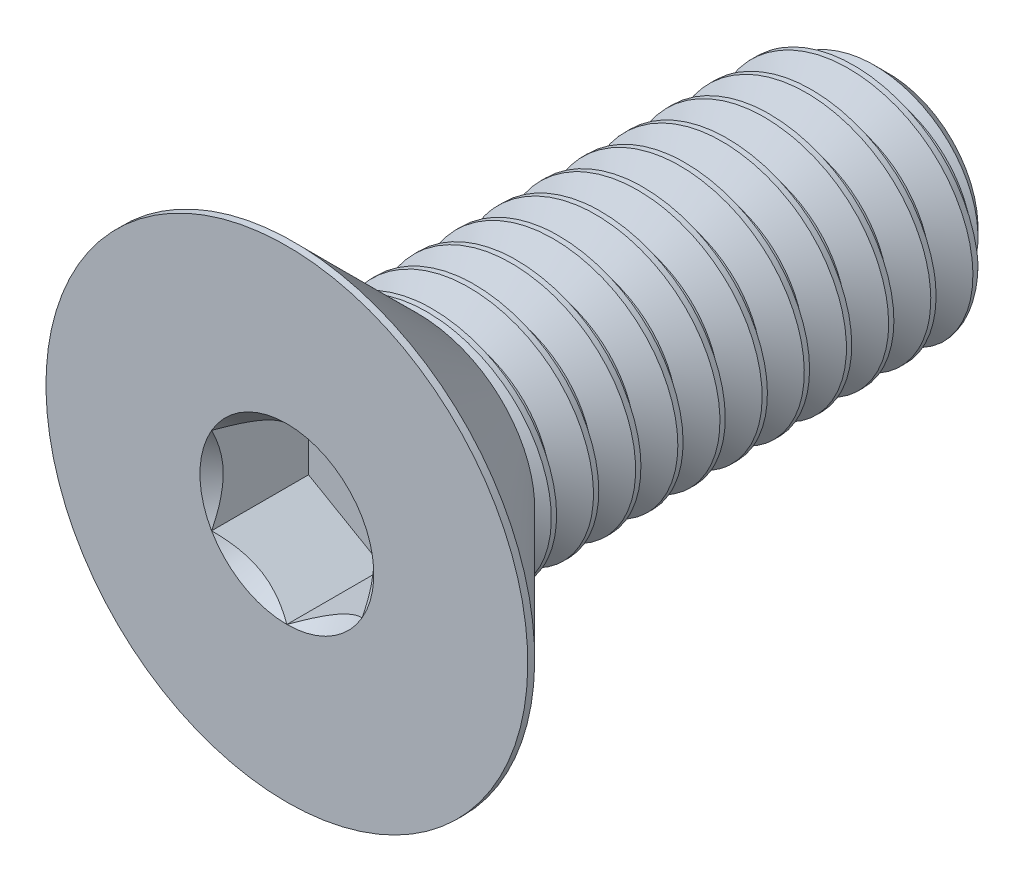
SolidWorks part; units mm, degrees
material "AISI 304"
ref_plane "Front" through (0, 0, 0) normal (0, 0, 1) x (1, 0, 0)
ref_plane "Top" through (0, 0, 0) normal (0, 1, 0) x (1, 0, 0)
ref_plane "Right" through (0, 0, 0) normal (1, 0, 0) x (0, 0, -1)
sketch "Sketch11" plane through (0, 0, 0) normal (1, 0, 0) x (0, 0, -1)
  line L0 (-5, 4) -> (5, 4) construction
  line L5 (-5, 4) -> (-5, -4) construction
  line L6 (5, 2) -> (5, -2) construction
  line L7 (-4.99, 1.25) -> (-4.99, -1.25) construction
  line L8 (4.9562, 2.0758) -> (5.6563, 2.0758) construction
  line L9 (5.6563, 2.0758) -> (5.3062, 1.4696) construction
  line L10 (5.3062, 1.4696) -> (4.9562, 2.0758) construction
  line L11 (5.2625, 1.5453) -> (5.35, 1.5453) construction
  line L12 (5.3062, 1.5453) -> (5.3062, 1.4696) construction
  line L13 (4.9781, 2.0379) -> (5.6344, 2.0379) construction
  line L14 (5.3062, 2.0758) -> (5.3062, 2) construction
  line L15 (5, 2) -> (5.6125, 2) construction
  line L17 (-4.885, 4) -> (-0.885, 0) construction
  line L18 (-0.885, 0) -> (-4.885, -4) construction
  point P3 (-2.7, 4)
  point P8 (0, 4)
  point P21 (5.3062, 2.0379)
  point P26 (-5, 0)
  point P28 (-4.99, 0)
  point P29 (5, 0)
  dimension "Length" = 10
  dimension "Head Diameter" = 8
  dimension "Thread Major Diameter" = 4
  dimension "Head Height" = 2.3
  dimension "Drive Size" = 2.5
  dimension "Thread Pitch" = 0.7
  dimension "D1" = 0.0875
  dimension "D2" = 0.01
  dimension "D3" = 0.115
  dimension "Countersink Angle" = 90
sketch "Sketch1" plane through (0, 0, 0) normal (1, 0, 0) x (0, 0, -1)
  line L2 (-2.7, 2) -> (5, 2)
  line L3 (5, 2) -> (5, 0)
  line L4 (-3.39, 2) -> (-3.39, 0)
  line L5 (-2.7, 2) -> (-3.39, 2)
  line L6 (-5, 4) -> (-5, -4) construction
  line L7 (5, 2) -> (5, -2) construction
  line L8 (-3.39, 0) -> (5, 0)
  dimension "D1" = 1.61
revolve "Revolve1" add sketch "Sketch1" angle 360 mid plane about L8
chamfer "Chamfer1" distance 0.525 angle 45 1 edges at (0, -2, -5)
sketch "Sketch7" plane through (0, 0, 0) normal (1, 0, 0) x (0, 0, -1)
  line L2 (-5, 4) -> (-4.885, 4)
  line L5 (-2.7, 1.815) -> (-2.7, 0)
  line L6 (-5, 4) -> (-5, 0)
  line L8 (-5, 4) -> (-5, -4) construction
  line L9 (-5, 0) -> (-2.7, 0)
  line L12 (-4.885, 4) -> (-2.7, 1.815)
  line L13 (-4.885, 4) -> (-0.885, 0) construction
revolve "Revolve2" add sketch "Sketch7" angle 360 mid plane about L9 region at (0, 1.5544, 3.9977)
ref_plane "Plane1" through (0, 0, 2.7) normal (0, 0, 1) x (1, 0, 0)
sketch "Sketch5" plane through (0, 0, 5) normal (0, 0, 1) x (1, 0, 0)
  line L1 (1.25, -0.7217) -> (1.25, 0.7217)
  line L2 (1.25, 0.7217) -> (0, 1.4434)
  line L3 (0, 1.4434) -> (-1.25, 0.7217)
  line L4 (-1.25, 0.7217) -> (-1.25, -0.7217)
  line L5 (-1.25, -0.7217) -> (0, -1.4434)
  line L6 (0, -1.4434) -> (1.25, -0.7217)
  circle A0 centre (0, 0) radius 1.25 construction
extrude "Cut-Extrude2" cut sketch "Sketch5" against normal blind 1.61
sketch "Sketch6" plane through (0, 0, 5) normal (0, 0, -1) x (-1, 0, 0)
  circle A0 centre (0, 0) radius 1.4434
extrude "Cut-Extrude3" cut sketch "Sketch6" along normal blind 1.61 draft 45
sketch "Sketch12" plane through (0, 0, -5) normal (0, 0, -1) x (-1, 0, 0)
  circle A0 centre (0, 0) radius 2 construction
  circle A1 centre (0, 0) radius 2
curve "Helix/Spiral1" pitch 0.7 height 10 radius 2 centre (0, 0, -5) axis (0, 0, 1) start towards (0, 1, 0)
sketch "Sketch13" plane through (0, 0, 0) normal (1, 0, 0) x (0, 0, -1)
  line L0 (4.9781, 2.0379) -> (5.6344, 2.0379)
  line L1 (5.6344, 2.0379) -> (5.35, 1.5453)
  line L2 (5.35, 1.5453) -> (5.2625, 1.5453)
  line L3 (5.2625, 1.5453) -> (4.9781, 2.0379)
sweep "Cut-Sweep1" cut profiles "Sketch13" path "Helix/Spiral1" align with end faces yes
combine bodies "Combine1" operation type add bodies to combine 113 127
equation "\"D1@Chamfer1\"=\"Thread Pitch@Sketch11\" * .75"
equation "\"D1@Cut-Extrude2\"= \"Head Height@Sketch11\" * .7"
equation "\"D1@Cut-Extrude3\" = \"D1@Cut-Extrude2\""
equation "\"D1@Sketch11\"=\"Thread Pitch@Sketch11\"/8"
equation "\"D3@Sketch11\"=\"Head Height@Sketch11\"*.05"
equation "\"D4@Helix/Spiral1\"=\"Thread Pitch@Sketch11\""
equation "\"D1@Sketch1\"=\"Head Height@Sketch11\"*.7"
equation "\"D3@Helix/Spiral1\"=\"Length@Sketch11\""
